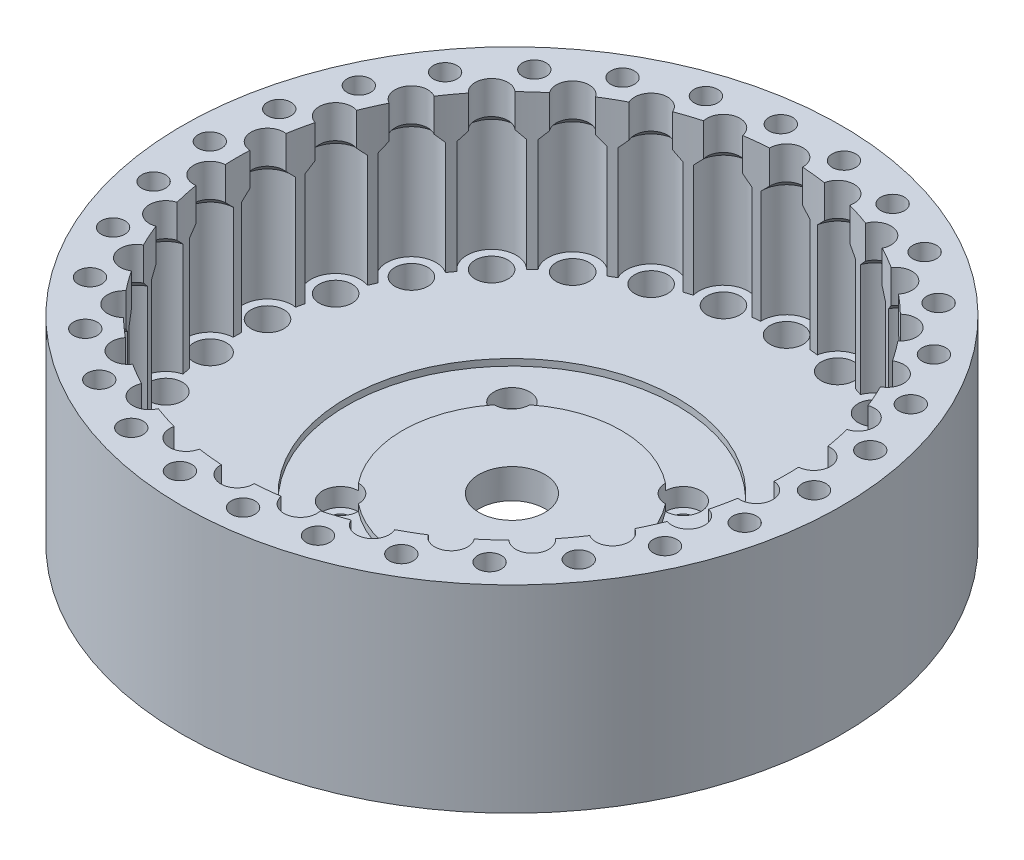
SolidWorks part; units mm, degrees
ref_plane "Front Plane" through (0, 0, 0) normal (0, 0, 1) x (1, 0, 0)
ref_plane "Top Plane" through (0, 0, 0) normal (0, 1, 0) x (1, 0, 0)
ref_plane "Right Plane" through (0, 0, 0) normal (1, 0, 0) x (0, 0, -1)
sketch "Sketch1" plane through (0, 0, 0) normal (0, 1, 0) x (1, 0, 0)
  circle A31 centre (0, 0) radius 60
  point P64 (0, 0)
  dimension "D1" = 120
extrude "Boss-Extrude1" add sketch "Sketch1" along normal blind 8
sketch "Sketch2" plane through (0, 8, 0) normal (0, 1, 0) x (1, 0, 0)
  circle A0 centre (0, 50) radius 3
  circle A1 centre (0, 50) radius 4.5 construction
  circle A2 centre (10.3956, 48.9074) radius 3
  circle A3 centre (20.3368, 45.6773) radius 3
  circle A4 centre (29.3893, 40.4508) radius 3
  circle A5 centre (37.1572, 33.4565) radius 3
  circle A6 centre (43.3013, 25) radius 3
  circle A7 centre (47.5528, 15.4508) radius 3
  circle A8 centre (49.7261, 5.2264) radius 3
  circle A9 centre (49.7261, -5.2264) radius 3
  circle A10 centre (47.5528, -15.4508) radius 3
  circle A11 centre (43.3013, -25) radius 3
  circle A12 centre (37.1572, -33.4565) radius 3
  circle A13 centre (29.3893, -40.4508) radius 3
  circle A14 centre (20.3368, -45.6773) radius 3
  circle A15 centre (10.3956, -48.9074) radius 3
  circle A16 centre (0, -50) radius 3
  circle A17 centre (-10.3956, -48.9074) radius 3
  circle A18 centre (-20.3368, -45.6773) radius 3
  circle A19 centre (-29.3893, -40.4508) radius 3
  circle A20 centre (-37.1572, -33.4565) radius 3
  circle A21 centre (-43.3013, -25) radius 3
  circle A22 centre (-47.5528, -15.4508) radius 3
  circle A23 centre (-49.7261, -5.2264) radius 3
  circle A24 centre (-49.7261, 5.2264) radius 3
  circle A25 centre (-47.5528, 15.4508) radius 3
  circle A26 centre (-43.3013, 25) radius 3
  circle A27 centre (-37.1572, 33.4565) radius 3
  circle A28 centre (-29.3893, 40.4508) radius 3
  circle A29 centre (-20.3368, 45.6773) radius 3
  circle A30 centre (-10.3956, 48.9074) radius 3
  point P64 (0, 0)
  dimension "D1" = 6
  dimension "D2" = 50
  dimension "D3" = 9
  dimension "D4" = 30
extrude "Cut-Extrude2" cut sketch "Sketch2" against normal blind 6
sketch "Sketch3" plane through (0, 8, 0) normal (0, 1, 0) x (1, 0, 0)
  circle A0 centre (0, 50) radius 3 construction
  circle A1 centre (0, 50) radius 3
  circle A2 centre (0, 50) radius 4.5
  circle A3 centre (10.3956, 48.9074) radius 4.5
  circle A4 centre (20.3368, 45.6773) radius 4.5
  circle A5 centre (29.3893, 40.4508) radius 4.5
  circle A6 centre (37.1572, 33.4565) radius 4.5
  circle A7 centre (43.3013, 25) radius 4.5
  circle A8 centre (47.5528, 15.4508) radius 4.5
  circle A9 centre (49.7261, 5.2264) radius 4.5
  circle A10 centre (49.7261, -5.2264) radius 4.5
  circle A11 centre (47.5528, -15.4508) radius 4.5
  circle A12 centre (43.3013, -25) radius 4.5
  circle A13 centre (37.1572, -33.4565) radius 4.5
  circle A14 centre (29.3893, -40.4508) radius 4.5
  circle A15 centre (20.3368, -45.6773) radius 4.5
  circle A16 centre (10.3956, -48.9074) radius 4.5
  circle A17 centre (0, -50) radius 4.5
  circle A18 centre (-10.3956, -48.9074) radius 4.5
  circle A19 centre (-20.3368, -45.6773) radius 4.5
  circle A20 centre (-29.3893, -40.4508) radius 4.5
  circle A21 centre (-37.1572, -33.4565) radius 4.5
  circle A22 centre (-43.3013, -25) radius 4.5
  circle A23 centre (-47.5528, -15.4508) radius 4.5
  circle A24 centre (-49.7261, -5.2264) radius 4.5
  circle A25 centre (-49.7261, 5.2264) radius 4.5
  circle A26 centre (-47.5528, 15.4508) radius 4.5
  circle A27 centre (-43.3013, 25) radius 4.5
  circle A28 centre (-37.1572, 33.4565) radius 4.5
  circle A29 centre (-29.3893, 40.4508) radius 4.5
  circle A30 centre (-20.3368, 45.6773) radius 4.5
  circle A31 centre (-10.3956, 48.9074) radius 4.5
  circle A32 centre (0, 0) radius 60 construction
  circle A33 centre (0, 0) radius 60
  circle A34 centre (0, 0) radius 50
  point P65 (0, 0)
  circle M33 centre (0, 0) radius 60
  dimension "D2" = 30
  dimension "D1" = 1.5
extrude "Boss-Extrude2" add sketch "Sketch3" along normal blind 28 contours A34 A17 A18 A19 A20 A21 A22 A23 A24 A25 A26 A27 A28 A29 A30 A31 A2 A3 A4 A5 A6 A7 A8 A9 A10 M33 region at (-58.3029, 8, 0)
sketch "Sketch4" plane through (0, 36, 0) normal (0, 1, 0) x (1, 0, 0)
  circle A0 centre (0, 50) radius 3 construction
  arc A1 (4.4954, 49.7975) -> (-4.4954, 49.7975) centre (0, 50) ccw construction
  arc A2 (2.9986, 49.91) -> (-2.9986, 49.91) centre (0, 50) ccw
  arc A3 (4.4954, 49.7975) -> (-4.4954, 49.7975) centre (0, 50) ccw
  arc A4 (4.4954, 49.7975) -> (2.9986, 49.91) centre (0, 0) ccw
  arc A5 (-2.9986, 49.91) -> (-4.4954, 49.7975) centre (0, 0) ccw
  arc A6 (13.31, 48.1959) -> (7.4438, 49.4428) centre (10.3956, 48.9074) ccw
  arc A7 (7.4438, 49.4428) -> (5.9563, 49.644) centre (0, 0) ccw
  arc A8 (14.7507, 47.7747) -> (5.9563, 49.644) centre (10.3956, 48.9074) ccw
  arc A9 (14.7507, 47.7747) -> (13.31, 48.1959) centre (0, 0) ccw
  arc A10 (23.0396, 44.3754) -> (17.5608, 46.8147) centre (20.3368, 45.6773) ccw
  arc A11 (17.5608, 46.8147) -> (16.1477, 47.3207) centre (0, 0) ccw
  arc A12 (24.3613, 43.6638) -> (16.1477, 47.3207) centre (20.3368, 45.6773) ccw
  arc A13 (24.3613, 43.6638) -> (23.0396, 44.3754) centre (0, 0) ccw
  arc A14 (31.7623, 38.6155) -> (26.9104, 42.1406) centre (29.3893, 40.4508) ccw
  arc A15 (26.9104, 42.1406) -> (25.6333, 42.9294) centre (0, 0) ccw
  arc A16 (32.9071, 37.6447) -> (25.6333, 42.9294) centre (29.3893, 40.4508) ccw
  arc A17 (32.9071, 37.6447) -> (31.7623, 38.6155) centre (0, 0) ccw
  arc A18 (39.0968, 31.1679) -> (35.0839, 35.6247) centre (37.1572, 33.4565) ccw
  arc A19 (35.0839, 35.6247) -> (33.9987, 36.6618) centre (0, 0) ccw
  arc A20 (40.0148, 29.9803) -> (33.9987, 36.6618) centre (37.1572, 33.4565) ccw
  arc A21 (40.0148, 29.9803) -> (39.0968, 31.1679) centre (0, 0) ccw
  arc A22 (44.7227, 22.3581) -> (41.724, 27.5519) centre (43.3013, 25) ccw
  arc A23 (41.724, 27.5519) -> (40.8782, 28.7919) centre (0, 0) ccw
  arc A24 (45.3736, 21.0056) -> (40.8782, 28.7919) centre (43.3013, 25) ccw
  arc A25 (45.3736, 21.0056) -> (44.7227, 22.3581) centre (0, 0) ccw
  arc A26 (48.3939, 12.5712) -> (46.5406, 18.2749) centre (47.5528, 15.4508) ccw
  arc A27 (46.5406, 18.2749) -> (45.9711, 19.6637) centre (0, 0) ccw
  arc A28 (48.7494, 11.1129) -> (45.9711, 19.6637) centre (47.5528, 15.4508) ccw
  arc A29 (48.7494, 11.1129) -> (48.3939, 12.5712) centre (0, 0) ccw
  arc A30 (49.95, 2.2348) -> (49.3231, 8.1992) centre (49.7261, 5.2264) ccw
  arc A31 (49.3231, 8.1992) -> (49.0548, 9.6761) centre (0, 0) ccw
  arc A32 (49.9946, 0.7344) -> (49.0548, 9.6761) centre (49.7261, 5.2264) ccw
  arc A33 (49.9946, 0.7344) -> (49.95, 2.2348) centre (0, 0) ccw
  arc A34 (49.3231, -8.1992) -> (49.95, -2.2348) centre (49.7261, -5.2264) ccw
  arc A35 (49.95, -2.2348) -> (49.9946, -0.7344) centre (0, 0) ccw
  arc A36 (49.0548, -9.6761) -> (49.9946, -0.7344) centre (49.7261, -5.2264) ccw
  arc A37 (49.0548, -9.6761) -> (49.3231, -8.1992) centre (0, 0) ccw
  arc A38 (46.5406, -18.2749) -> (48.3939, -12.5712) centre (47.5528, -15.4508) ccw
  arc A39 (48.3939, -12.5712) -> (48.7494, -11.1129) centre (0, 0) ccw
  arc A40 (45.9711, -19.6637) -> (48.7494, -11.1129) centre (47.5528, -15.4508) ccw
  arc A41 (45.9711, -19.6637) -> (46.5406, -18.2749) centre (0, 0) ccw
  arc A42 (41.724, -27.5519) -> (44.7227, -22.3581) centre (43.3013, -25) ccw
  arc A43 (44.7227, -22.3581) -> (45.3736, -21.0056) centre (0, 0) ccw
  arc A44 (40.8782, -28.7919) -> (45.3736, -21.0056) centre (43.3013, -25) ccw
  arc A45 (40.8782, -28.7919) -> (41.724, -27.5519) centre (0, 0) ccw
  arc A46 (35.0839, -35.6247) -> (39.0968, -31.1679) centre (37.1572, -33.4565) ccw
  arc A47 (39.0968, -31.1679) -> (40.0148, -29.9803) centre (0, 0) ccw
  arc A48 (33.9987, -36.6618) -> (40.0148, -29.9803) centre (37.1572, -33.4565) ccw
  arc A49 (33.9987, -36.6618) -> (35.0839, -35.6247) centre (0, 0) ccw
  arc A50 (26.9104, -42.1406) -> (31.7623, -38.6155) centre (29.3893, -40.4508) ccw
  arc A51 (31.7623, -38.6155) -> (32.9071, -37.6447) centre (0, 0) ccw
  arc A52 (25.6333, -42.9294) -> (32.9071, -37.6447) centre (29.3893, -40.4508) ccw
  arc A53 (25.6333, -42.9294) -> (26.9104, -42.1406) centre (0, 0) ccw
  arc A54 (17.5608, -46.8147) -> (23.0396, -44.3754) centre (20.3368, -45.6773) ccw
  arc A55 (23.0396, -44.3754) -> (24.3613, -43.6638) centre (0, 0) ccw
  arc A56 (16.1477, -47.3207) -> (24.3613, -43.6638) centre (20.3368, -45.6773) ccw
  arc A57 (16.1477, -47.3207) -> (17.5608, -46.8147) centre (0, 0) ccw
  arc A58 (7.4438, -49.4428) -> (13.31, -48.1959) centre (10.3956, -48.9074) ccw
  arc A59 (13.31, -48.1959) -> (14.7507, -47.7747) centre (0, 0) ccw
  arc A60 (5.9563, -49.644) -> (14.7507, -47.7747) centre (10.3956, -48.9074) ccw
  arc A61 (5.9563, -49.644) -> (7.4438, -49.4428) centre (0, 0) ccw
  arc A62 (-2.9986, -49.91) -> (2.9986, -49.91) centre (0, -50) ccw
  arc A63 (2.9986, -49.91) -> (4.4954, -49.7975) centre (0, 0) ccw
  arc A64 (-4.4954, -49.7975) -> (4.4954, -49.7975) centre (0, -50) ccw
  arc A65 (-4.4954, -49.7975) -> (-2.9986, -49.91) centre (0, 0) ccw
  arc A66 (-13.31, -48.1959) -> (-7.4438, -49.4428) centre (-10.3956, -48.9074) ccw
  arc A67 (-7.4438, -49.4428) -> (-5.9563, -49.644) centre (0, 0) ccw
  arc A68 (-14.7507, -47.7747) -> (-5.9563, -49.644) centre (-10.3956, -48.9074) ccw
  arc A69 (-14.7507, -47.7747) -> (-13.31, -48.1959) centre (0, 0) ccw
  arc A70 (-23.0396, -44.3754) -> (-17.5608, -46.8147) centre (-20.3368, -45.6773) ccw
  arc A71 (-17.5608, -46.8147) -> (-16.1477, -47.3207) centre (0, 0) ccw
  arc A72 (-24.3613, -43.6638) -> (-16.1477, -47.3207) centre (-20.3368, -45.6773) ccw
  arc A73 (-24.3613, -43.6638) -> (-23.0396, -44.3754) centre (0, 0) ccw
  arc A74 (-31.7623, -38.6155) -> (-26.9104, -42.1406) centre (-29.3893, -40.4508) ccw
  arc A75 (-26.9104, -42.1406) -> (-25.6333, -42.9294) centre (0, 0) ccw
  arc A76 (-32.9071, -37.6447) -> (-25.6333, -42.9294) centre (-29.3893, -40.4508) ccw
  arc A77 (-32.9071, -37.6447) -> (-31.7623, -38.6155) centre (0, 0) ccw
  arc A78 (-39.0968, -31.1679) -> (-35.0839, -35.6247) centre (-37.1572, -33.4565) ccw
  arc A79 (-35.0839, -35.6247) -> (-33.9987, -36.6618) centre (0, 0) ccw
  arc A80 (-40.0148, -29.9803) -> (-33.9987, -36.6618) centre (-37.1572, -33.4565) ccw
  arc A81 (-40.0148, -29.9803) -> (-39.0968, -31.1679) centre (0, 0) ccw
  arc A82 (-44.7227, -22.3581) -> (-41.724, -27.5519) centre (-43.3013, -25) ccw
  arc A83 (-41.724, -27.5519) -> (-40.8782, -28.7919) centre (0, 0) ccw
  arc A84 (-45.3736, -21.0056) -> (-40.8782, -28.7919) centre (-43.3013, -25) ccw
  arc A85 (-45.3736, -21.0056) -> (-44.7227, -22.3581) centre (0, 0) ccw
  arc A86 (-48.3939, -12.5712) -> (-46.5406, -18.2749) centre (-47.5528, -15.4508) ccw
  arc A87 (-46.5406, -18.2749) -> (-45.9711, -19.6637) centre (0, 0) ccw
  arc A88 (-48.7494, -11.1129) -> (-45.9711, -19.6637) centre (-47.5528, -15.4508) ccw
  arc A89 (-48.7494, -11.1129) -> (-48.3939, -12.5712) centre (0, 0) ccw
  arc A90 (-49.95, -2.2348) -> (-49.3231, -8.1992) centre (-49.7261, -5.2264) ccw
  arc A91 (-49.3231, -8.1992) -> (-49.0548, -9.6761) centre (0, 0) ccw
  arc A92 (-49.9946, -0.7344) -> (-49.0548, -9.6761) centre (-49.7261, -5.2264) ccw
  arc A93 (-49.9946, -0.7344) -> (-49.95, -2.2348) centre (0, 0) ccw
  arc A94 (-49.3231, 8.1992) -> (-49.95, 2.2348) centre (-49.7261, 5.2264) ccw
  arc A95 (-49.95, 2.2348) -> (-49.9946, 0.7344) centre (0, 0) ccw
  arc A96 (-49.0548, 9.6761) -> (-49.9946, 0.7344) centre (-49.7261, 5.2264) ccw
  arc A97 (-49.0548, 9.6761) -> (-49.3231, 8.1992) centre (0, 0) ccw
  arc A98 (-46.5406, 18.2749) -> (-48.3939, 12.5712) centre (-47.5528, 15.4508) ccw
  arc A99 (-48.3939, 12.5712) -> (-48.7494, 11.1129) centre (0, 0) ccw
  arc A100 (-45.9711, 19.6637) -> (-48.7494, 11.1129) centre (-47.5528, 15.4508) ccw
  arc A101 (-45.9711, 19.6637) -> (-46.5406, 18.2749) centre (0, 0) ccw
  arc A102 (-41.724, 27.5519) -> (-44.7227, 22.3581) centre (-43.3013, 25) ccw
  arc A103 (-44.7227, 22.3581) -> (-45.3736, 21.0056) centre (0, 0) ccw
  arc A104 (-40.8782, 28.7919) -> (-45.3736, 21.0056) centre (-43.3013, 25) ccw
  arc A105 (-40.8782, 28.7919) -> (-41.724, 27.5519) centre (0, 0) ccw
  arc A106 (-35.0839, 35.6247) -> (-39.0968, 31.1679) centre (-37.1572, 33.4565) ccw
  arc A107 (-39.0968, 31.1679) -> (-40.0148, 29.9803) centre (0, 0) ccw
  arc A108 (-33.9987, 36.6618) -> (-40.0148, 29.9803) centre (-37.1572, 33.4565) ccw
  arc A109 (-33.9987, 36.6618) -> (-35.0839, 35.6247) centre (0, 0) ccw
  arc A110 (-26.9104, 42.1406) -> (-31.7623, 38.6155) centre (-29.3893, 40.4508) ccw
  arc A111 (-31.7623, 38.6155) -> (-32.9071, 37.6447) centre (0, 0) ccw
  arc A112 (-25.6333, 42.9294) -> (-32.9071, 37.6447) centre (-29.3893, 40.4508) ccw
  arc A113 (-25.6333, 42.9294) -> (-26.9104, 42.1406) centre (0, 0) ccw
  arc A114 (-17.5608, 46.8147) -> (-23.0396, 44.3754) centre (-20.3368, 45.6773) ccw
  arc A115 (-23.0396, 44.3754) -> (-24.3613, 43.6638) centre (0, 0) ccw
  arc A116 (-16.1477, 47.3207) -> (-24.3613, 43.6638) centre (-20.3368, 45.6773) ccw
  arc A117 (-16.1477, 47.3207) -> (-17.5608, 46.8147) centre (0, 0) ccw
  arc A118 (-7.4438, 49.4428) -> (-13.31, 48.1959) centre (-10.3956, 48.9074) ccw
  arc A119 (-13.31, 48.1959) -> (-14.7507, 47.7747) centre (0, 0) ccw
  arc A120 (-5.9563, 49.644) -> (-14.7507, 47.7747) centre (-10.3956, 48.9074) ccw
  arc A121 (-5.9563, 49.644) -> (-7.4438, 49.4428) centre (0, 0) ccw
  point P185 (0, 0)
  dimension "D1" = 30
extrude "Boss-Extrude3" add sketch "Sketch4" against normal blind 6
chamfer "Chamfer1" distance 1.5 angle 45 30 edges at (0, 30, -54.5) (47.1984, 30, -27.25) (40.5014, 30, -36.4676) (32.0343, 30, -44.0914) (22.1671, 30, -49.7882) (11.3312, 30, -53.309) (-11.3312, 30, -53.309) (-22.1671, 30, -49.7882) (-32.0343, 30, -44.0914) (-40.5014, 30, -36.4676) (-47.1984, 30, -27.25) (-51.8326, 30, -16.8414) (-54.2014, 30, -5.6968) (-54.2014, 30, 5.6968) (-51.8326, 30, 16.8414) (-47.1984, 30, 27.25) (-40.5014, 30, 36.4676) (-32.0343, 30, 44.0914) (-22.1671, 30, 49.7882) (-11.3312, 30, 53.309) (0, 30, 54.5) (11.3312, 30, 53.309) (22.1671, 30, 49.7882) (32.0343, 30, 44.0914) (40.5014, 30, 36.4676) (47.1984, 30, 27.25) (51.8326, 30, 16.8414) (54.2014, 30, 5.6968) (54.2014, 30, -5.6968) (51.8326, 30, -16.8414)
sketch "Sketch5" plane through (0, 8, 0) normal (0, 1, 0) x (1, 0, 0)
  circle A0 centre (0, 0) radius 6
  dimension "D1" = 12
extrude "Cut-Extrude3" cut sketch "Sketch5" against normal through all
hole_wizard "CBORE for M3 Hex Socket Head Cap Screw1" positions "Sketch6" profile "Sketch8" counterbore size "M3" standard "DIN" end condition through all
sketch "Sketch6" plane through (0, 8, 0) normal (0, 1, 0) x (1, 0, 0)
  line L1 (15.6, -15.6) -> (-15.6, -15.6)
  line L2 (15.6, -15.6) -> (15.6, 15.6)
  line L3 (15.6, 15.6) -> (-15.6, 15.6)
  line L4 (-15.6, -15.6) -> (-15.6, 15.6)
  line L5 (15.6, -15.6) -> (-15.6, 15.6) construction
  line L6 (15.6, 15.6) -> (-15.6, -15.6) construction
  point P1 (-15.6, 15.6)
  point P4 (15.6, -15.6)
  point P5 (15.6, 15.6)
  point P6 (-15.6, -15.6)
  point P36 (0, 0)
  dimension "D1" = 31.2
sketch "Sketch8" plane through (-15.6, 8, -15.6) normal (1, 0, 0) x (0, 0, 1)
  line L0 (0, 0) -> (0, 8)
  line L1 (0, 8) -> (1.8, 8)
  line L3 (1.8, 8) -> (1.8, 4.5)
  line L4 (1.8, 4.5) -> (3.25, 4.5)
  line L5 (3.25, 4.5) -> (3.25, 0)
  line L7 (3.25, 0) -> (0, 0)
  line L11 (0, -6.35) -> (0, 107.95) construction
  dimension "Thru Hole Dia." = 3.6
  dimension "Thru Hole Depth" = 8
  dimension "C'Bore Dia." = 6.5
  dimension "C'Bore Depth" = 4.5
sketch "Sketch10" plane through (0, 0, 0) normal (0, -1, 0) x (1, 0, 0)
  circle A0 centre (0, 0) radius 11.25
  dimension "D1" = 22.5
extrude "Cut-Extrude5" cut sketch "Sketch10" against normal blind 2.6
sketch "Sketch11" plane through (0, 8, 0) normal (0, 1, 0) x (1, 0, 0)
  circle A0 centre (0, 0) radius 19.9
  circle A1 centre (0, 0) radius 30.1
  dimension "D1" = 39.8
  dimension "D2" = 60.2
extrude "Cut-Extrude6" cut sketch "Sketch11" against normal blind 1.2
hole_wizard "Ø4.3 (4.3) Diameter Hole1" positions "Sketch12" profile "Sketch13" hole size "Ø4.3" standard "DIN" end condition through all
sketch "Sketch12" plane through (0, 36, 0) normal (0, 1, 0) x (1, 0, 0)
  line L0 (0, 0) -> (-5.2264, 49.7261) construction
  line L1 (-5.2264, 49.7261) -> (-6.9978, 66.5801) construction
  arc A0 (-2.9986, 49.91) -> (-7.4438, 49.4428) centre (0, 0) ccw construction
  point P10 (-5.7491, 54.6987)
  point P21 (5.7491, 54.6987)
  point P22 (16.9959, 52.3081)
  point P23 (27.5, 47.6314)
  point P24 (36.8022, 40.873)
  point P25 (44.4959, 32.3282)
  point P26 (50.245, 22.3705)
  point P27 (53.7981, 11.4351)
  point P28 (55, 0)
  point P29 (53.7981, -11.4351)
  point P30 (50.245, -22.3705)
  point P31 (44.4959, -32.3282)
  point P32 (36.8022, -40.873)
  point P33 (27.5, -47.6314)
  point P34 (16.9959, -52.3081)
  point P35 (5.7491, -54.6987)
  point P36 (-5.7491, -54.6987)
  point P37 (-16.9959, -52.3081)
  point P38 (-27.5, -47.6314)
  point P39 (-36.8022, -40.873)
  point P40 (-44.4959, -32.3282)
  point P41 (-50.245, -22.3705)
  point P42 (-53.7981, -11.4351)
  point P43 (-55, 0)
  point P44 (-53.7981, 11.4351)
  point P45 (-50.245, 22.3705)
  point P46 (-44.4959, 32.3282)
  point P47 (-36.8022, 40.873)
  point P48 (-27.5, 47.6314)
  point P49 (-16.9959, 52.3081)
  dimension "D2" = 30
  dimension "D1" = 55
sketch "Sketch13" plane through (-16.9959, 36, -52.3081) normal (1, 0, 0) x (0, 0, 1)
  line L0 (0, 0) -> (0, 36)
  line L1 (0, 36) -> (2.15, 36)
  line L2 (2.15, 36) -> (2.15, 0)
  line L5 (2.15, 0) -> (0, 0)
  line L11 (0, -6.35) -> (0, 107.95) construction
  dimension "Thru Hole Dia." = 4.3
  dimension "Thru Hole Depth" = 36
